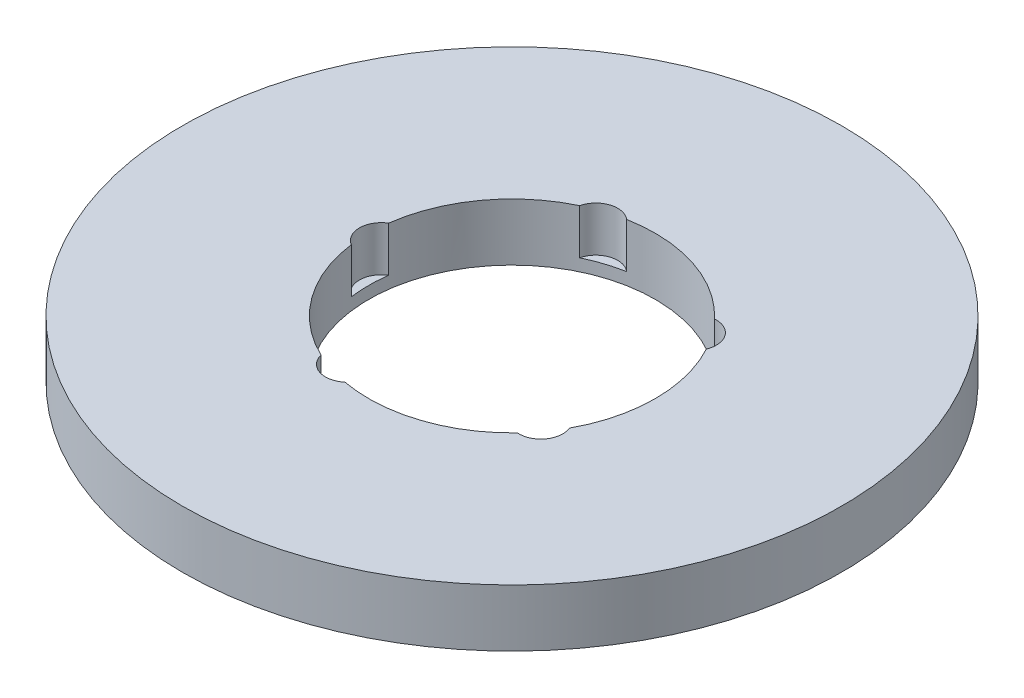
SolidWorks part; units mm, degrees
ref_plane "Front Plane" through (0, 0, 0) normal (0, 0, 1) x (1, 0, 0)
ref_plane "Top Plane" through (0, 0, 0) normal (0, 1, 0) x (1, 0, 0)
ref_plane "Right Plane" through (0, 0, 0) normal (1, 0, 0) x (0, 0, -1)
sketch "Sketch1" plane through (0, 0, 0) normal (0, 1, 0) x (1, 0, 0)
  circle A0 centre (0, 0) radius 57.5
  dimension "FLANGE_OD" = 115
extrude "Boss-Extrude1" add sketch "Sketch1" along normal blind 10
sketch "Sketch2" plane through (0, 0, 0) normal (0, 1, 0) x (1, 0, 0)
  circle A0 centre (0, 0) radius 25
  dimension "BORE_D" = 50
extrude "Cut-Extrude1" cut sketch "Sketch2" along normal through all
sketch "Sketch3" plane through (0, 10, 0) normal (0, 1, 0) x (1, 0, 0)
  circle A0 centre (0, 0) radius 22.8023 construction
  circle A1 centre (-22.8023, 0) radius 3.8087
  dimension "BOLT_D" = 7.6174
  dimension "BOLT_PCD" = 45.6045
extrude "Cut-Extrude2" cut sketch "Sketch3" against normal blind 7.8793
pattern_circular "CirPattern1" count 5 over 360 about axis through (0, 0, 0) along (0, 1, 0) of "Cut-Extrude2"
